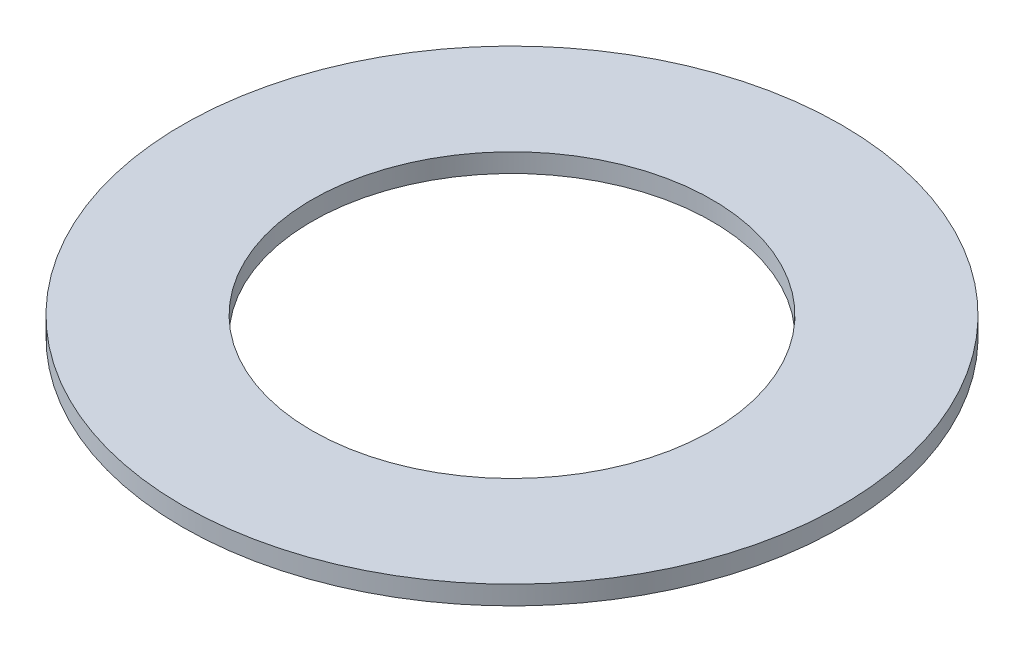
SolidWorks part; units mm, degrees
ref_plane "Front Plane" through (0, 0, 0) normal (0, 0, 1) x (1, 0, 0)
ref_plane "Top Plane" through (0, 0, 0) normal (0, 1, 0) x (1, 0, 0)
ref_plane "Right Plane" through (0, 0, 0) normal (1, 0, 0) x (0, 0, -1)
sketch "Sketch1" plane through (0, 0, 0) normal (0, 1, 0) x (1, 0, 0)
  circle A0 centre (0, 0) radius 70
  dimension "FLANGE_OD" = 140
extrude "Boss-Extrude1" add sketch "Sketch1" along normal blind 4
sketch "Sketch2" plane through (0, 0, 0) normal (0, 1, 0) x (1, 0, 0)
  circle A0 centre (0, 0) radius 42.5
  dimension "BORE_D" = 85
extrude "Cut-Extrude1" cut sketch "Sketch2" along normal through all
sketch "Sketch3" plane through (0, 4, 0) normal (0, 1, 0) x (1, 0, 0)
  circle A0 centre (0, 0) radius 26.9356 construction
  circle A1 centre (-26.9356, 0) radius 1.5621
  dimension "BOLT_D" = 3.1242
  dimension "BOLT_PCD" = 53.8713
extrude "Cut-Extrude2" cut sketch "Sketch3" against normal blind 3.0578 rebuild error yes
pattern_circular "CirPattern1" count 6 over 360 rebuild error yes
